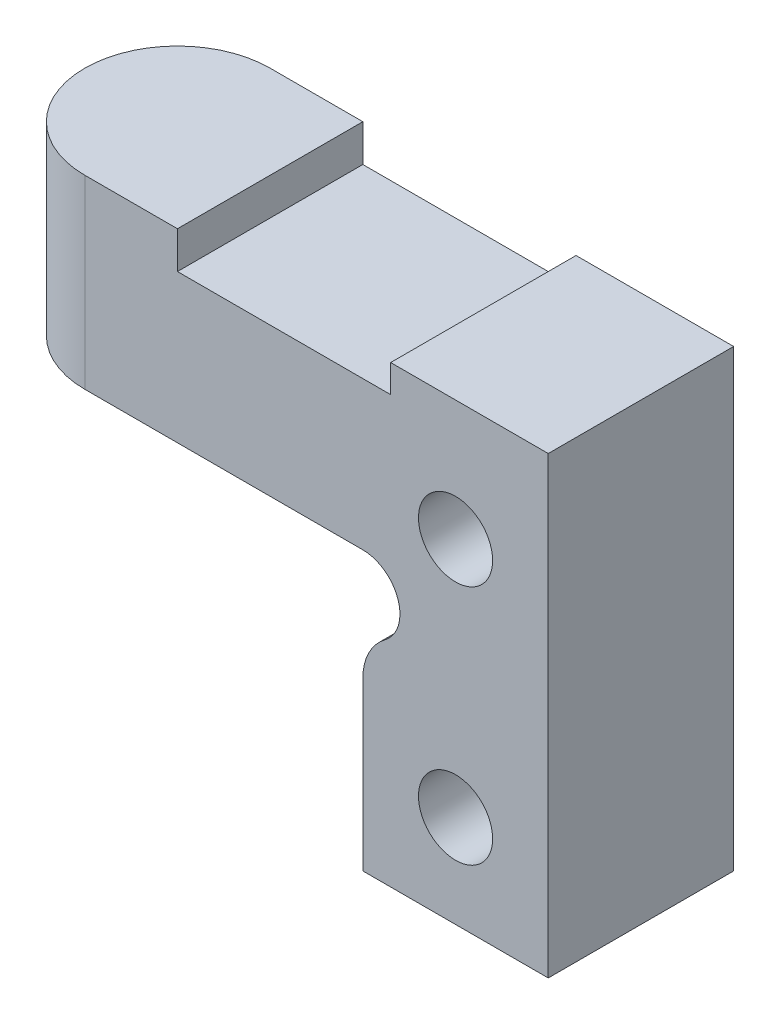
SolidWorks part; units mm, degrees
ref_plane "Front Plane" through (0, 0, 0) normal (0, 0, 1) x (1, 0, 0)
ref_plane "Top Plane" through (0, 0, 0) normal (0, 1, 0) x (1, 0, 0)
ref_plane "Right Plane" through (0, 0, 0) normal (1, 0, 0) x (0, 0, -1)
sketch "Sketch1" plane through (0, 0, 0) normal (0, 1, 0) x (1, 0, 0)
  line L1 (0, 0) -> (20, 0)
  line L2 (0, 0) -> (0, 10)
  line L3 (0, 10) -> (30, 10)
  line L4 (30, 0) -> (30, 10)
  line L5 (20, 0) -> (30, 0)
  dimension "D1" = 30
  dimension "D2" = 10
  dimension "D3" = 10
extrude "Boss-Extrude1" add sketch "Sketch1" along normal blind 10
sketch "Sketch2" plane through (0, 10, 0) normal (0, 1, 0) x (1, 0, 0)
  line L1 (21.5, 10) -> (10, 10)
  line L2 (21.5, 10) -> (21.5, -7.2465)
  line L3 (21.5, -7.2465) -> (10, -7.2465)
  line L4 (10, 10) -> (10, -7.2465)
  line L5 (0, 10) -> (0, 0) construction
  line L6 (30, 0) -> (30, 10) construction
  dimension "D1" = 10
  dimension "D2" = 8.5
extrude "Cut-Extrude1" cut sketch "Sketch2" against normal blind 2
fillet "Fillet1" radius 5 2 edges at (0, 5, -10) (0, 5, 0)
sketch "Sketch4" plane through (0, 0, 0) normal (0, -1, 0) x (1, 0, 0)
  line L0 (6.5, -10) -> (6.5, 0) construction
  line L1 (30, 0) -> (30, -10) construction
  circle A0 centre (6.5, -5) radius 2.15
  dimension "D1" = 4.3
  dimension "D2" = 23.5
extrude "Cut-Extrude4" cut sketch "Sketch4" against normal blind 5
sketch "Sketch6" plane through (0, 0, 0) normal (0, -1, 0) x (1, 0, 0)
  line L0 (5, 0) -> (30, 0) construction
  line L1 (20, 0) -> (30, 0)
  line L2 (20, 0) -> (20, -10)
  line L3 (20, -10) -> (30, -10)
  line L4 (30, 0) -> (30, -10)
extrude "Boss-Extrude2" add sketch "Sketch6" along normal blind 15
sketch "Sketch5" plane through (0, 0, 0) normal (0, 0, 1) x (1, 0, 0)
  line L0 (30, 10) -> (30, -15) construction
  line L1 (21.5, 8) -> (10, 8) construction
  circle A0 centre (25, 3) radius 2
  circle A1 centre (25, -10) radius 2
  dimension "D3" = 4
  dimension "D1" = 5
  dimension "D2" = 5
  dimension "D4" = 13
extrude "Cut-Extrude5" cut sketch "Sketch5" against normal blind 7
sketch "Sketch7" plane through (0, 10, 0) normal (0, 1, 0) x (1, 0, 0)
  line L4 (30, 10) -> (21.5, 10)
  line L5 (21.5, 10) -> (21.5, 0)
  line L6 (21.5, 0) -> (30, 0)
  line L7 (30, 0) -> (30, 10)
  line L8 (30, 10) -> (21.5, 10)
  line L9 (21.5, 10) -> (21.5, 0)
  line L10 (21.5, 0) -> (30, 0)
  line L11 (30, 0) -> (30, 10)
  dimension "D1" = 0
extrude "Cut-Extrude6" cut sketch "Sketch7" against normal blind 0.5
sketch "Sketch8" plane through (0, 0, -10) normal (0, 0, -1) x (-1, 0, 0)
  line L0 (-20, -15) -> (-20, 0) construction
  circle A0 centre (-20, -2) radius 2
  dimension "D1" = 4
extrude "Cut-Extrude7" cut sketch "Sketch8" against normal through all and the other way through all
fillet "Fillet2" radius 3 1 edges at (20, -4, -5)
